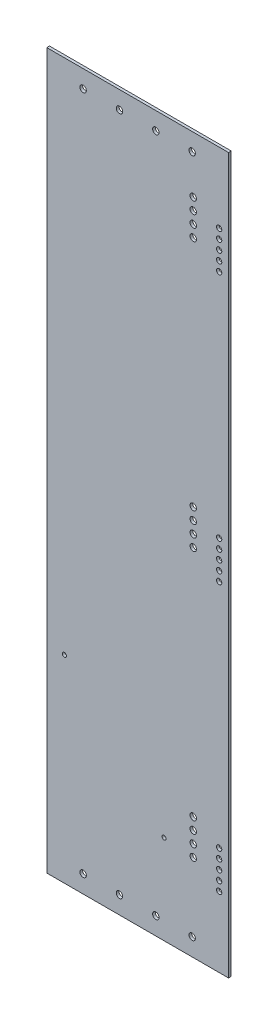
SolidWorks part; units mm, degrees
material "5052-H32"
ref_plane "Front Plane" through (0, 0, 0) normal (0, 0, 1) x (1, 0, 0)
ref_plane "Top Plane" through (0, 0, 0) normal (0, 1, 0) x (1, 0, 0)
ref_plane "Right Plane" through (0, 0, 0) normal (1, 0, 0) x (0, 0, -1)
sketch "Sketch1" plane through (0, 0, 0) normal (0, 0, 1) x (1, 0, 0)
  line L0 (55, 0) -> (-55, 0) construction
  line L1 (-77.5, 304.8) -> (77.5, 304.8)
  line L2 (-77.5, 304.8) -> (-77.5, -304.8)
  line L3 (-77.5, -304.8) -> (77.5, -304.8)
  line L4 (77.5, 304.8) -> (77.5, -304.8)
  line L5 (-77.5, 304.8) -> (77.5, -304.8) construction
  line L6 (-77.5, -304.8) -> (77.5, 304.8) construction
  point P0 (0, 0)
  point P5 (69.5, 244.8)
  point P7 (69.5, 228.8)
  point P8 (69.5, 236.8)
  point P9 (69.5, 220.8)
  point P10 (69.5, 212.8)
  point P11 (69.5, 8)
  point P12 (69.5, 16)
  point P13 (69.5, -212.8)
  point P14 (69.5, -228.8)
  point P15 (69.5, -220.8)
  point P16 (69.5, -236.8)
  point P17 (69.5, -244.8)
  point P18 (69.5, -8)
  point P19 (69.5, -16)
  point P20 (-46.5, 289.795)
  point P21 (-15.5, 289.795)
  point P22 (69.5, 0)
  point P23 (15.5, 289.795)
  point P24 (46.5, 289.795)
  point P25 (22.5, -228.6)
  point P26 (-62.5, -136.1)
  point P29 (46.5, -289.795)
  point P30 (15.5, -289.795)
  point P31 (-15.5, -289.795)
  point P32 (-46.5, -289.795)
  point P33 (47.4, 226.8)
  point P34 (47.4, 236.8)
  point P35 (47.4, 246.8)
  point P36 (47.4, 256.8)
  point P37 (47.4, 8)
  point P38 (47.4, 18)
  point P39 (47.4, -2)
  point P40 (47.4, 28)
  point P41 (47.4, -220.8)
  point P42 (47.4, -210.8)
  point P43 (47.4, -230.8)
  point P44 (47.4, -200.8)
  point P45 (0, 0)
  point P46 (0, 0)
  point P47 (0, 0)
  point P48 (0, 0)
  point P49 (0, 0)
  point P50 (0, 0)
  point P51 (0, 0)
  point P52 (0, 0)
  point P53 (0, 0)
  point P54 (0, 0)
  point P55 (0, 0)
  dimension "D1" = 609.6
  dimension "D2" = 155
  dimension "D3" = 8
  dimension "D4" = 60
  dimension "D5" = 8
  dimension "D6" = 8
  dimension "D7" = 8
  dimension "D8" = 8
  dimension "D9" = 60
  dimension "D10" = 8
  dimension "D11" = 8
  dimension "D12" = 8
  dimension "D13" = 8
  dimension "D14" = 8
  dimension "D15" = 8
  dimension "D16" = 8
  dimension "D17" = 8
  dimension "D18" = 8
  dimension "D19" = 8
  dimension "D20" = 31
  dimension "D21" = 31
  dimension "D22" = 31
  dimension "D23" = 31
  dimension "D24" = 15.005
  dimension "D25" = 92.5
  dimension "D26" = 85
  dimension "D27" = 76.2
  dimension "D28" = 15
  dimension "D29" = 10
  dimension "D30" = 10
  dimension "D31" = 10
  dimension "D32" = 22.1
  dimension "D33" = 10
  dimension "D34" = 10
  dimension "D35" = 10
  dimension "D36" = 22.1
  dimension "D37" = 10
  dimension "D38" = 10
  dimension "D39" = 10
  dimension "D40" = 22.1
extrude "Boss-Extrude1" add sketch "Sketch1" along normal blind 2.305
hole_wizard "M4 Clearance Hole1" positions "Sketch3" profile "Sketch5" hole size "M4" standard "ANSI Metric" end condition through all
sketch "Sketch3" plane through (0, 0, 2.305) normal (0, 0, 1) x (1, 0, 0)
  point P4 (69.5, 228.8)
  point P9 (69.5, 244.8)
  point P12 (69.5, 236.8)
  point P15 (69.5, 220.8)
  point P18 (69.5, 212.8)
  point P21 (69.5, 16)
  point P24 (69.5, 8)
  point P27 (69.5, 0)
  point P30 (69.5, -8)
  point P33 (69.5, -16)
  point P36 (69.5, -212.8)
  point P39 (69.5, -220.8)
  point P42 (69.5, -228.8)
  point P45 (69.5, -236.8)
  point P48 (69.5, -244.8)
sketch "Sketch5" plane through (69.5, 228.8, 2.305) normal (1, 0, 0) x (0, -1, 0)
  line L0 (0, 0) -> (0, 2.305)
  line L1 (0, 2.305) -> (2.25, 2.305)
  line L2 (2.25, 2.305) -> (2.25, 0)
  line L5 (2.25, 0) -> (0, 0)
  line L11 (0, -6.35) -> (0, 107.95) construction
  dimension "Thru Hole Dia." = 4.5
  dimension "Thru Hole Depth" = 2.305
hole_wizard "M5 Clearance Hole1" positions "Sketch6" profile "Sketch7" hole size "M5" standard "ANSI Metric" end condition through all
sketch "Sketch6" plane through (0, 0, 2.305) normal (0, 0, 1) x (1, 0, 0)
  point P0 (-46.5, -289.795)
  point P3 (-15.5, -289.795)
  point P6 (15.5, -289.795)
  point P9 (46.5, -289.795)
  point P12 (-46.5, 289.795)
  point P15 (-15.5, 289.795)
  point P18 (15.5, 289.795)
  point P21 (46.5, 289.795)
  point P24 (47.4, -230.8)
  point P27 (47.4, -220.8)
  point P30 (47.4, -210.8)
  point P33 (47.4, -200.8)
  point P36 (47.4, -2)
  point P39 (47.4, 8)
  point P42 (47.4, 18)
  point P45 (47.4, 28)
  point P48 (47.4, 226.8)
  point P51 (47.4, 236.8)
  point P54 (47.4, 246.8)
  point P57 (47.4, 256.8)
sketch "Sketch7" plane through (-46.5, -289.795, 2.305) normal (1, 0, 0) x (0, -1, 0)
  line L0 (0, 0) -> (0, 2.305)
  line L1 (0, 2.305) -> (2.75, 2.305)
  line L2 (2.75, 2.305) -> (2.75, 0)
  line L5 (2.75, 0) -> (0, 0)
  line L11 (0, -6.35) -> (0, 107.95) construction
  dimension "Thru Hole Dia." = 5.5
  dimension "Thru Hole Depth" = 2.305
hole_wizard "Ø3.5 (3.5) Diameter Hole1" positions "Sketch8" profile "Sketch9" hole size "Ø3.5" standard "ANSI Metric" end condition through all
sketch "Sketch8" plane through (0, 0, 0) normal (0, 0, -1) x (-1, 0, 0)
  point P0 (-22.5, -228.6)
  point P3 (62.5, -136.1)
sketch "Sketch9" plane through (22.5, -228.6, 0) normal (1, 0, 0) x (0, 1, 0)
  line L0 (0, 0) -> (0, 2.305)
  line L1 (0, 2.305) -> (1.75, 2.305)
  line L2 (1.75, 2.305) -> (1.75, 0)
  line L5 (1.75, 0) -> (0, 0)
  line L11 (0, -6.35) -> (0, 107.95) construction
  dimension "Thru Hole Dia." = 3.5
  dimension "Thru Hole Depth" = 2.305
